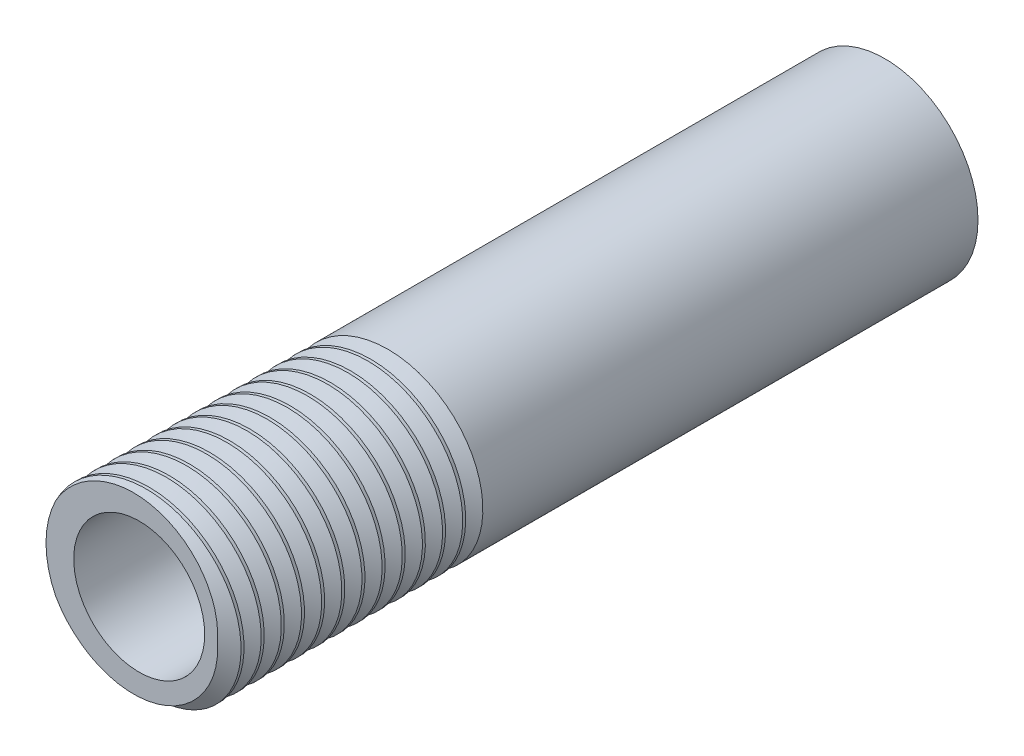
SolidWorks part; units mm, degrees
ref_plane "Front Plane" through (0, 0, 0) normal (0, 0, 1) x (1, 0, 0)
ref_plane "Top Plane" through (0, 0, 0) normal (0, 1, 0) x (1, 0, 0)
ref_plane "Right Plane" through (0, 0, 0) normal (1, 0, 0) x (0, 0, -1)
sketch "Sketch1" plane through (0, 0, 0) normal (0, 0, 1) x (1, 0, 0)
  circle A0 centre (0, 0) radius 6.5
  circle A1 centre (0, 0) radius 9.25
  dimension "D1" = 18.5
  dimension "D2" = 13
extrude "Boss-Extrude1" add sketch "Sketch1" along normal blind 74
sketch "Sketch2" plane through (0, 0, 74) normal (0, 0, 1) x (1, 0, 0)
  circle A0 centre (0, 0) radius 9.25
  circle A2 centre (0, 0) radius 9.25 construction
curve "Helix/Spiral1" pitch 2 height 25 radius 9.25 centre (0, 0, 74) axis (0, 0, -1) start towards (1, 0, 0)
sketch "Sketch5" plane through (0, 0, 0) normal (0, 1, 0) x (1, 0, 0)
  line L0 (-9.25, -72.0961) -> (9.25, -72.0961) construction
  line L1 (9.25, -74) -> (9.25, 0) construction
  line L2 (-9.25, 0) -> (-9.25, -74) construction
  line L9 (9.25, -74) -> (9.25, 0) construction
  line L10 (0, -72.0961) -> (0, -75.3544) construction
  line L12 (7.773, -74) -> (9.25, -73.1473)
  line L13 (9.25, -73.1473) -> (9.25, -74.8527)
  line L14 (9.25, -74.8527) -> (7.773, -74)
  line L15 (-9.25, -74) -> (9.25, -74) construction
  point P10 (9.25, -90.1436)
  dimension "D1" = 60
  dimension "D2" = 7.773
sweep "Cut-Sweep4" cut profiles "Sketch5" path "Helix/Spiral1" align with end faces yes
